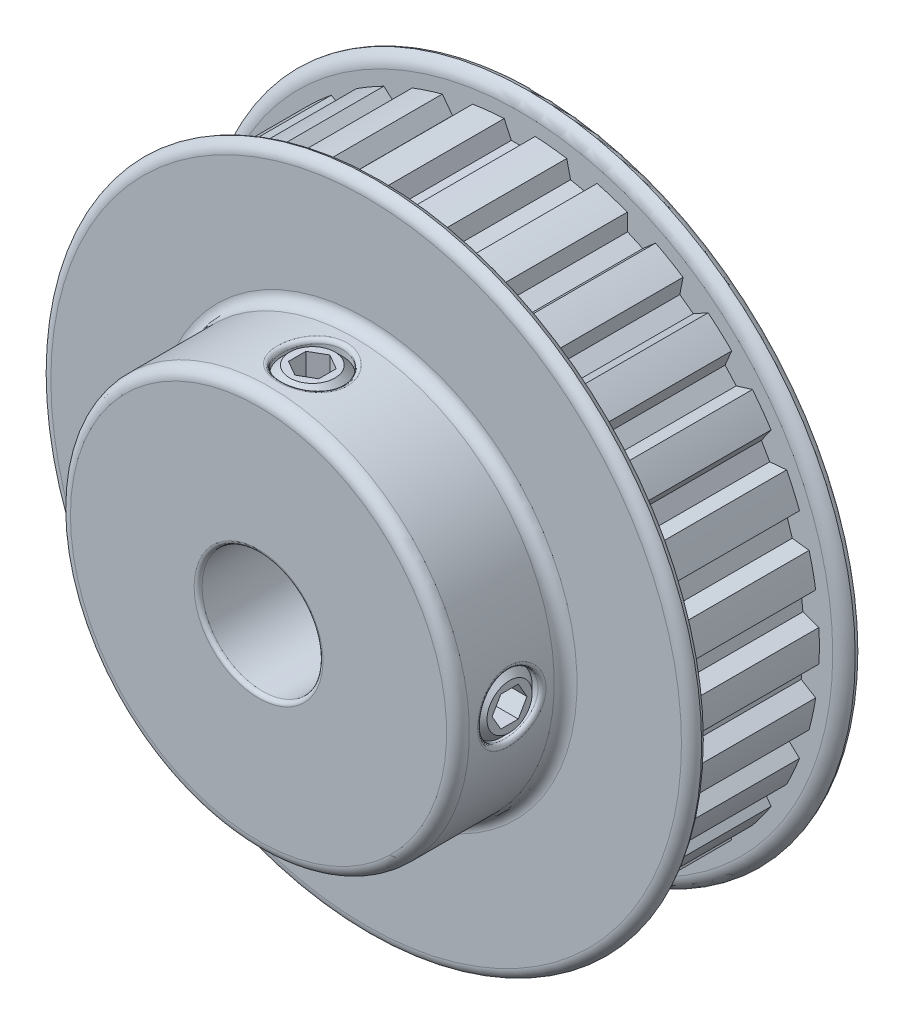
SolidWorks part; units mm, degrees
ref_plane "Front Plane" through (0, 0, 0) normal (0, 0, 1) x (1, 0, 0)
ref_plane "Top Plane" through (0, 0, 0) normal (0, 1, 0) x (1, 0, 0)
ref_plane "Right Plane" through (0, 0, 0) normal (1, 0, 0) x (0, 0, -1)
sketch "Sketch1" plane through (0, 0, 0) normal (0, 0, 1) x (1, 0, 0)
  line L0 (-1.2827, 24.7496) -> (-0.6905, 23.4796)
  line L1 (-0.6905, 23.4796) -> (0.6905, 23.4796)
  line L2 (0.6905, 23.4796) -> (1.2827, 24.7496)
  line L3 (-1.2827, 24.7496) -> (1.2827, 24.7496)
  line L4 (0, 0) -> (0, 23.4796) construction
  line L5 (0, 23.4796) -> (0, 25.7656) construction
  circle A0 centre (0, 0) radius 24.25 construction
  circle A1 centre (0, 0) radius 27 construction
  circle A2 centre (0, 0) radius 24.7828 construction
  point P6 (0, 24.7496)
  point P11 (0, 24.25)
  point P13 (0, 27)
  point P14 (0, 24.7828)
  dimension "Pitch Diameter" = 48.5
  dimension "OD" = 54
  dimension "D5" = 50
  dimension "D6" = 2.5654
  dimension "D4" = 1.27
  dimension "D3" = 2.286
  dimension "D2" = 1.5156
sketch "Sketch2" plane through (0, 0, 0) normal (1, 0, 0) x (0, 0, -1)
  line L0 (-11.55, 5) -> (11.55, 5) construction
  line L1 (-11.55, 5) -> (-11.55, 16.5) construction
  line L2 (-11.55, 16.5) -> (-2.65, 16.5) construction
  line L3 (-2.65, 16.5) -> (-2.65, 27) construction
  line L4 (-2.65, 27) -> (-1.15, 27) construction
  line L5 (-1.15, 27) -> (-1.15, 24.7828) construction
  line L6 (-1.15, 24.7828) -> (10.05, 24.7828) construction
  line L7 (10.05, 24.7828) -> (10.05, 27) construction
  line L8 (10.05, 27) -> (11.55, 27) construction
  line L9 (11.55, 27) -> (11.55, 5) construction
  line L10 (-11.55, 0) -> (11.55, 0) construction
  line L13 (-2.65, 27) -> (-1.9, 27) construction
  line L14 (-1.15, 25.8914) -> (-1.15, 24.7828) construction
  line L15 (10.05, 24.7828) -> (10.05, 25.8914) construction
  line L16 (10.8, 27) -> (11.55, 27) construction
  arc A0 (-1.15, 25.8914) -> (-1.9, 27) centre (-2.3443, 25.8914) ccw construction
  arc A1 (10.05, 25.8914) -> (10.8, 27) centre (11.2443, 25.8914) cw construction
  point P12 (-1.15, 25.8914)
  point P14 (-1.9, 27)
  point P20 (10.05, 25.8914)
  point P21 (10.8, 27)
  point P25 (10.05, 0)
  point P26 (-1.15, 0)
  dimension "Overall Width" = 23.1
  dimension "Outside Width" = 14.2
  dimension "Inside Width" = 11.2
  dimension "Hub Diameter" = 33
  dimension "For Shaft Diameter" = 10
sketch "Sketch7" plane through (0, 0, 0) normal (1, 0, 0) x (0, 0, -1)
  line L0 (-11.55, 5) -> (-11.55, 16.5) construction
  line L1 (-11.55, 16.5) -> (-2.65, 16.5) construction
  line L2 (-2.65, 16.5) -> (-2.65, 27) construction
  line L3 (-2.65, 27) -> (-1.9, 27) construction
  line L4 (-1.15, 25.8914) -> (-1.15, 24.7828) construction
  line L5 (-1.15, 24.7828) -> (10.05, 24.7828) construction
  line L6 (10.05, 24.7828) -> (10.05, 25.8914) construction
  line L7 (10.8, 27) -> (11.55, 27) construction
  line L8 (11.55, 27) -> (11.55, 5) construction
  line L9 (-11.55, 5) -> (11.55, 5) construction
  line L10 (-11.55, 5) -> (-11.55, 16.5)
  line L11 (-11.55, 16.5) -> (-2.65, 16.5)
  line L12 (-2.65, 16.5) -> (-2.65, 27)
  line L13 (-2.65, 27) -> (-1.9, 27)
  line L14 (-1.15, 25.8914) -> (-1.15, 24.7828)
  line L15 (-1.15, 24.7828) -> (10.05, 24.7828)
  line L16 (10.05, 24.7828) -> (10.05, 25.8914)
  line L17 (10.8, 27) -> (11.55, 27)
  line L18 (11.55, 27) -> (11.55, 5)
  line L19 (-11.55, 5) -> (11.55, 5)
  arc A0 (-1.15, 25.8914) -> (-1.9, 27) centre (-2.3443, 25.8914) ccw construction
  arc A1 (10.8, 27) -> (10.05, 25.8914) centre (11.2443, 25.8914) ccw construction
  arc A2 (-1.15, 25.8914) -> (-1.9, 27) centre (-2.3443, 25.8914) ccw
  arc A3 (10.8, 27) -> (10.05, 25.8914) centre (11.2443, 25.8914) ccw
revolve "Revolve1" add sketch "Sketch7" angle 360 about L10
sketch "Sketch3" plane through (0, 0, 0) normal (0, 0, 1) x (1, 0, 0)
  line L0 (-0.6905, 23.4796) -> (0.6905, 23.4796) construction
  line L1 (0.6905, 23.4796) -> (1.2827, 24.7496) construction
  line L2 (-1.2827, 24.7496) -> (-0.6905, 23.4796) construction
  line L3 (-0.6905, 23.4796) -> (0.6905, 23.4796)
  line L4 (0.6905, 23.4796) -> (1.2827, 24.7496)
  line L5 (-1.2827, 24.7496) -> (-0.6905, 23.4796)
  arc A1 (1.2827, 24.7496) -> (-1.2827, 24.7496) centre (0, 0) ccw
  circle A2 centre (0, 0) radius 24.7828 construction
extrude "Cut-Extrude1" cut sketch "Sketch3" against normal up to vertex (10.05 mm away) from vertex up to point (0, 24.7828, -10.05) starting at point (0, 24.7828, 1.15)
pattern_circular "CirPattern1" count 30 over 360 about axis through (0, 0, 11.55) along (0, 0, -1) of "Cut-Extrude1" reverse direction yes
sketch "Sketch4" plane through (0, 0, 0) normal (0, 1, 0) x (1, 0, 0)
  line L0 (0, -2.65) -> (0, -11.55) construction
  line L3 (0, -11.55) -> (0, 11.55) construction
  line L4 (-16.5, -2.65) -> (16.5, -2.65) construction
  line L5 (-16.5, -11.55) -> (16.5, -11.55) construction
  circle A0 centre (0, -7.1) radius 2.5
  dimension "D1" = 5
extrude "Cut-Extrude2" cut sketch "Sketch4" along normal through all
ref_plane "Plane1" through (0, 0, 7.1) normal (0, 0, 1) x (1, 0, 0)
sketch "Sketch5" plane through (0, 0, 7.1) normal (0, 0, 1) x (1, 0, 0)
  line L0 (0, 0) -> (0, 16.5) construction
  line L1 (-2.5, 16.3095) -> (-2.5, 4.3301) construction
  line L2 (-2.5, 16.3095) -> (-2.5, 4.3301) construction
  line L3 (0, 16.3095) -> (0, 5)
  line L4 (0, 5) -> (-1.865, 5)
  line L5 (-2.5, 15.6745) -> (-2.5, 5.635)
  line L6 (-1.865, 16.3095) -> (0, 16.3095)
  line L7 (-2.5, 15.6745) -> (-1.865, 16.3095)
  line L8 (-2.5, 5.635) -> (-1.865, 5)
  line L9 (0, 27) -> (0, 5) construction
  line L10 (0, 5) -> (0, 16.5) construction
  point P13 (-2.5, 5)
  point P15 (-2.5, 16.3095)
revolve "Revolve2" add sketch "Sketch5" angle 360 mid plane about L0
sketch "Sketch6" plane through (0, 16.3095, 0) normal (0, -1, 0) x (-1, 0, 0)
  line L1 (0, -5.6566) -> (-1.25, -6.3783)
  line L2 (-1.25, -6.3783) -> (-1.25, -7.8217)
  line L3 (-1.25, -7.8217) -> (0, -8.5434)
  line L4 (0, -8.5434) -> (1.25, -7.8217)
  line L5 (1.25, -7.8217) -> (1.25, -6.3783)
  line L6 (1.25, -6.3783) -> (0, -5.6566)
  circle A0 centre (0, -7.1) radius 1.25 construction
  dimension "D1" = 2.5
extrude "Cut-Extrude3" cut sketch "Sketch6" along normal blind 1.875
pattern_circular "CirPattern2" count 2 every 90 about axis through (0, 0, 11.55) along (0, 0, -1) of "Cut-Extrude2", "Revolve2", "Cut-Extrude3"
fillet "Fillet1" radius 0.9429 4 edges at (27, 0, -11.55) (27, 0, 2.65) (16.5, 0, 2.65) (16.5, 0, 11.55)
fillet "Fillet2" radius 0.33 4 edges at (5, 0, 11.55) (16.4911, -0.5429, 9.5403) (0.5429, 16.4911, 9.5403) (5, 0, -11.55)
equation "\"D1@Sketch4\" = \"For Shaft Diameter@Sketch2\"/2"
equation "\"D1@Sketch6\" = \"D1@Sketch4\"/2"
equation "\"D1@Cut-Extrude3\" = \"D1@Sketch6\"*.75"
equation "\"D1@Fillet1\"=\"Hub Diameter@Sketch2\" / 35"
equation "\"D2@Sketch1\"=\"Pitch Diameter@Sketch1\"/32"
equation "\"D1@Fillet2\"=\"Hub Diameter@Sketch2\"*.01"
